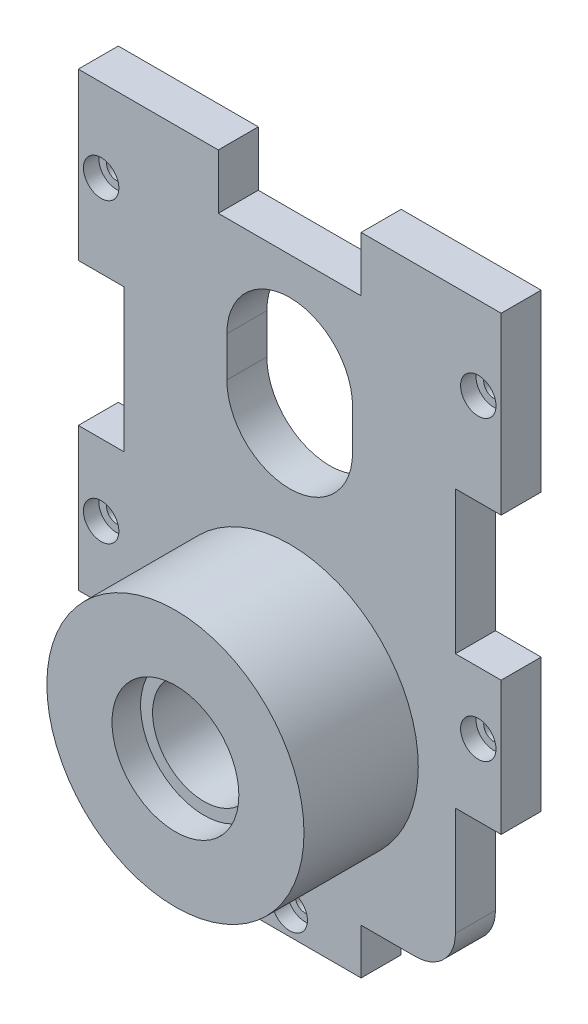
SolidWorks part; units mm, degrees
ref_plane "Alzado" through (0, 0, 0) normal (0, 0, 1) x (1, 0, 0)
ref_plane "Planta" through (0, 0, 0) normal (0, 1, 0) x (1, 0, 0)
ref_plane "Vista lateral" through (0, 0, 0) normal (1, 0, 0) x (0, 0, -1)
sketch "Croquis2" plane through (0, 0, 0) normal (0, 0, 1) x (1, 0, 0)
  line L0 (-30.7866, 48.816) -> (-5.7866, 48.816)
  line L1 (-5.7866, 48.816) -> (-5.7866, 39.2053)
  line L2 (-5.7866, 39.2053) -> (-30.7866, 39.2053)
  line L3 (-30.7866, 48.816) -> (-30.7866, 39.2053)
  line L5 (-22.5241, 25.0911) -> (-22.5241, 24.7943)
  line L7 (-18.1703, 25.0911) -> (-18.1703, 24.7943)
  line L8 (-5.7866, 48.816) -> (18.7134, 48.816)
  line L9 (-55.2866, 48.816) -> (-30.7866, 48.816)
  line L10 (18.7134, 48.816) -> (18.7134, 18.2053)
  line L11 (-55.2866, 48.816) -> (-55.2866, 19.816)
  line L12 (-55.2866, 19.816) -> (-47.2866, 19.816)
  line L13 (-47.2866, 19.816) -> (-47.2866, 39.2053)
  line L14 (-47.2866, 39.2053) -> (-30.7866, 39.2053)
  line L15 (18.7134, 18.2053) -> (10.7134, 18.2053)
  line L16 (10.7134, 18.2053) -> (10.7134, 39.2053)
  line L17 (10.7134, 39.2053) -> (-5.7866, 39.2053)
  line L18 (-55.2866, 19.816) -> (-55.2866, -5.184)
  line L19 (-55.2866, -5.184) -> (-47.2866, -5.184)
  line L20 (-47.2866, -5.184) -> (-47.2866, 19.816)
  line L21 (10.7134, 18.2053) -> (10.7134, -6.7947)
  line L22 (18.7134, 18.2053) -> (18.7134, -6.7947)
  line L23 (10.7134, -6.7947) -> (18.7134, -6.7947)
  line L24 (-55.2866, -5.184) -> (-55.2866, -30.184)
  line L25 (18.7134, -5.184) -> (18.7134, -30.184)
  line L26 (-47.2866, -5.184) -> (-47.2866, -30.184)
  line L28 (10.7134, -5.184) -> (10.7134, -30.184)
  line L29 (-55.2866, -30.184) -> (-47.2866, -30.184)
  line L30 (18.7134, -30.184) -> (10.7134, -30.184)
  line L31 (-55.2866, -30.184) -> (-55.2866, -49.184)
  line L32 (18.7134, -30.184) -> (18.7134, -49.184)
  line L34 (-47.2866, -30.184) -> (-47.2866, -49.184)
  line L35 (10.7134, -30.184) -> (10.7134, -49.184)
  line L36 (-47.2866, -49.184) -> (-55.2866, -49.184)
  line L37 (10.7134, -49.184) -> (18.7134, -49.184)
  line L38 (-40.2866, -56.184) -> (-30.7866, -56.184)
  line L39 (3.7134, -56.184) -> (3.7134, -64.184)
  line L40 (-30.7866, -56.184) -> (-30.7866, -64.184)
  line L42 (-30.7866, -64.184) -> (-40.2866, -64.184)
  line L43 (-30.7866, -56.184) -> (-5.7866, -56.184)
  line L44 (-40.2866, -64.184) -> (-40.2866, -56.184)
  line L45 (-5.7866, -56.184) -> (-5.7866, -64.184)
  line L46 (-5.7866, -64.184) -> (-30.7866, -64.184)
  line L47 (3.7134, -64.184) -> (-5.7866, -64.184)
  line L48 (-5.7866, -56.184) -> (3.7134, -56.184)
  line L50 (-7.2866, 21.7053) -> (-7.2866, 14.7053)
  line L52 (-29.2866, 21.7053) -> (-29.2866, 14.7053)
  arc A0 (-55.2866, -49.184) -> (-40.2866, -64.184) centre (-40.2866, -49.184) ccw
  arc A1 (18.7134, -49.184) -> (3.7134, -64.184) centre (3.7134, -49.184) cw
  arc A2 (-47.2866, -49.184) -> (-40.2866, -56.184) centre (-40.2866, -49.184) ccw
  arc A3 (3.7134, -56.184) -> (10.7134, -49.184) centre (3.7134, -49.184) ccw
  circle A4 centre (-18.2866, -27.184) radius 9
  arc A5 (-7.2866, 21.7053) -> (-29.2866, 21.7053) centre (-18.2866, 21.7053) ccw
  arc A7 (-29.2866, 14.7053) -> (-7.2866, 14.7053) centre (-18.2866, 14.7053) ccw
  circle A16 centre (-18.2866, -27.184) radius 22.5
  circle A17 centre (-18.2866, -27.184) radius 11.1
extrude "Saliente-Extruir1" add sketch "Croquis2" along normal blind 7 contours L48 A3 L35 L28 L21 L16 L17 L2 L14 L13 L20 L26 L34 A2 L38 L43 A16 A7 L52 A5 L50 | L17 L16 L15 L10 L8 L1 | L13 L14 L3 L9 L11 L12 | L24 L29 L26 L19 | L46 L45 L43 L40 | L30 L25 L23 L28 region at (-31.1663, 44.0106, 0) region at (6.4634, 48.4239, 0) region at (-18.2866, -3.6342, 0) region at (-51.2866, -17.684, 0) region at (14.7134, -18.4894, 0) region at (-18.2866, -60.184, 0)
extrude "Saliente-Extruir2" add sketch "Croquis2<4>" along normal blind 22 separate body contours A17 A4 region at (-29.0727, -27.184, 0)
sketch "Croquis2<4>" plane through (0, 0, 0) normal (0, 0, 1) x (1, 0, 0) same geometry as "Croquis2"
extrude "Saliente-Extruir3" add sketch "Croquis2<5>" along normal blind 27 contours A16 A17 region at (-40.1502, -27.184, 0)
sketch "Croquis2<5>" plane through (0, 0, 0) normal (0, 0, 1) x (1, 0, 0) same geometry as "Croquis2"
sketch "Croquis3" plane through (0, 0, 7) normal (0, 0, 1) x (1, 0, 0)
  circle A0 centre (-51.2866, 34.316) radius 1.75
  circle A1 centre (-51.2866, -17.684) radius 1.75
  circle A2 centre (-18.2866, -60.184) radius 1.75
  circle A3 centre (14.7134, -17.684) radius 1.75
  circle A4 centre (14.7134, 34.316) radius 1.75
extrude "Cortar-Extruir1" cut sketch "Croquis3" against normal blind 7
sketch "Croquis4" plane through (0, 0, 7) normal (0, 0, 1) x (1, 0, 0)
  circle A0 centre (-51.2866, -17.684) radius 3.1
  circle A1 centre (-51.2866, 34.316) radius 3.1
  circle A2 centre (14.7134, 34.316) radius 3.1
  circle A3 centre (14.7134, -17.684) radius 3.1
  circle A4 centre (-18.2866, -60.184) radius 3.1
extrude "Cortar-Extruir2" cut sketch "Croquis4" against normal blind 2.7
